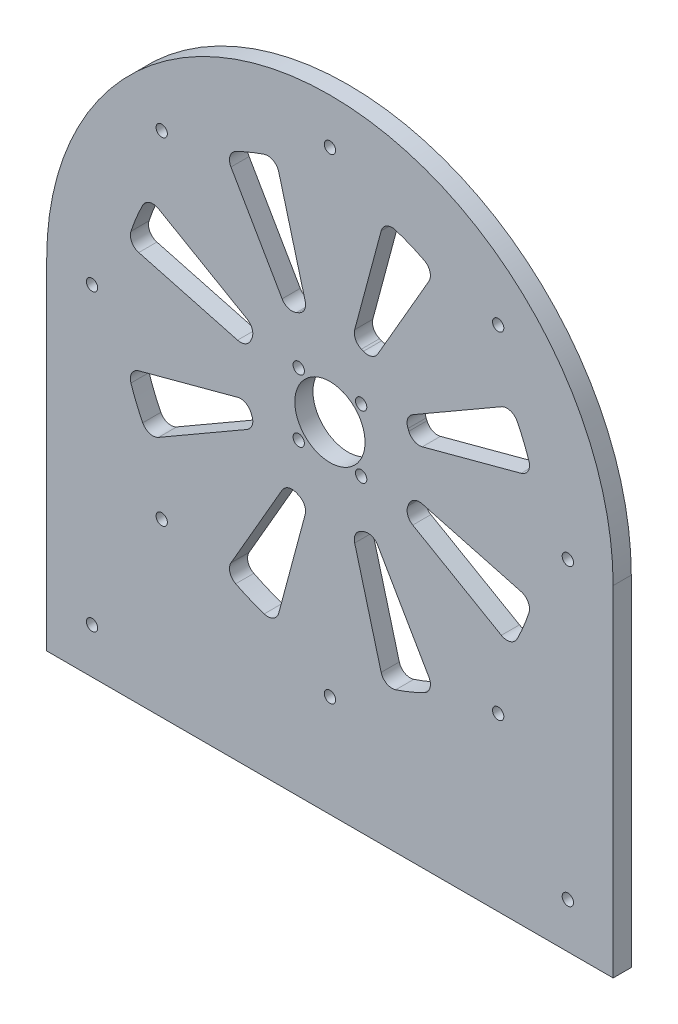
SolidWorks part; units mm, degrees
material "Delrin 2700 NC010, Low Viscosity Acetal Copolymer (SS)"
ref_plane "Ön Düzlem" through (0, 0, 0) normal (0, 0, 1) x (1, 0, 0)
ref_plane "Üst Düzlem" through (0, 0, 0) normal (0, 1, 0) x (1, 0, 0)
ref_plane "Sağ Düzlem" through (0, 0, 0) normal (1, 0, 0) x (0, 0, -1)
sketch "Sketch1" plane through (0, 0, 0) normal (0, 0, 1) x (1, 0, 0)
  line L1 (-250, -300) -> (250, -300)
  line L2 (-250, -300) -> (-250, 0)
  line L4 (250, -300) -> (250, 0)
  arc A0 (250, 0) -> (-250, 0) centre (0, 0) ccw
  dimension "D1" = 500
  dimension "D2" = 300
extrude "Boss-Extrude1" add sketch "Sketch1" along normal blind 16
sketch "Sketch3" plane through (0, 0, 0) normal (0, 0, -1) x (-1, 0, 0)
  circle A0 centre (0, 0) radius 31
  circle A1 centre (0, 0) radius 39 construction
  circle A2 centre (-27.55, 27.6043) radius 5
  circle A3 centre (27.55, 27.6043) radius 5
  circle A4 centre (27.55, -27.6043) radius 5
  circle A5 centre (-27.55, -27.6043) radius 5
  circle A6 centre (0, 0) radius 210 construction
  circle A7 centre (0, 210) radius 5
  circle A8 centre (148.4924, 148.4924) radius 5
  circle A9 centre (210, 0) radius 5
  circle A10 centre (148.4924, -148.4924) radius 5
  circle A11 centre (0, -210) radius 5
  circle A12 centre (-148.4924, -148.4924) radius 5
  circle A13 centre (-210, 0) radius 5
  circle A14 centre (-148.4924, 148.4924) radius 5
  point P17 (0, 0)
  point P33 (0, 0)
  dimension "D1" = 62
  dimension "D2" = 10
  dimension "D3" = 78
  dimension "D5" = 420
  dimension "D6" = 10
  dimension "D4" = 55.1
  dimension "D7" = 8
extrude "Cut-Extrude1" cut sketch "Sketch3" against normal through all
sketch "Sketch4" plane through (0, 0, 0) normal (0, 0, -1) x (-1, 0, 0)
  line L0 (0, 0) -> (0, 275.7905) construction
  line L1 (42.2049, 73.101) -> (87.357, 151.3068)
  line L2 (21.8468, 81.5335) -> (45.2193, 168.7608)
  arc A0 (29.5982, 68.9126) -> (27.7995, 69.6576) centre (0, 0) ccw
  circle A1 centre (0, 0) radius 250.1702 construction
  arc A2 (58.0145, 175.6682) -> (83.1937, 165.2386) centre (0, 0) cw
  arc A3 (58.0145, 175.6682) -> (45.2193, 168.7608) centre (54.8786, 166.1726) ccw
  arc A4 (21.8468, 81.5335) -> (27.7995, 69.6576) centre (31.5061, 78.9453) ccw
  arc A5 (29.5982, 68.9126) -> (42.2049, 73.101) centre (33.5446, 78.101) ccw
  arc A6 (83.1937, 165.2386) -> (87.357, 151.3068) centre (78.6968, 156.3068) cw
  dimension "D1" = 150
  dimension "D2" = 15
  dimension "D3" = 30
  dimension "D4" = 185
  dimension "D5" = 10
  dimension "D6" = 10
extrude "Cut-Extrude2" cut sketch "Sketch4" against normal through all
pattern_circular "CirPattern1" count 8 over 360 about axis through (0, 0, 0) along (0, 0, 1) of "Cut-Extrude2"
sketch "Sketch7" plane through (0, 0, 0) normal (0, 0, -1) x (-1, 0, 0)
  line L0 (-250, -300) -> (-250, 0) construction
  line L1 (250, -300) -> (-250, -300) construction
  line L2 (250, 0) -> (250, -300) construction
  circle A0 centre (-210, -260) radius 5
  circle A1 centre (210, -260) radius 5
  dimension "D1" = 10
  dimension "D4" = 10
  dimension "D2" = 40
  dimension "D3" = 40
  dimension "D5" = 40
  dimension "D6" = 40
extrude "Cut-Extrude4" cut sketch "Sketch7" against normal through all
sketch "Sketch5" plane through (0, 0, 0) normal (0, 0, -1) x (-1, 0, 0)
  text T0 "   Gökhan ÇAKAL - Ozan KEYSAN\r\nAxial Flux Permanent Magnet Machine" font "Consolas" height in points 48
extrude "Cut-Extrude3" cut sketch "Sketch5" against normal blind 1
